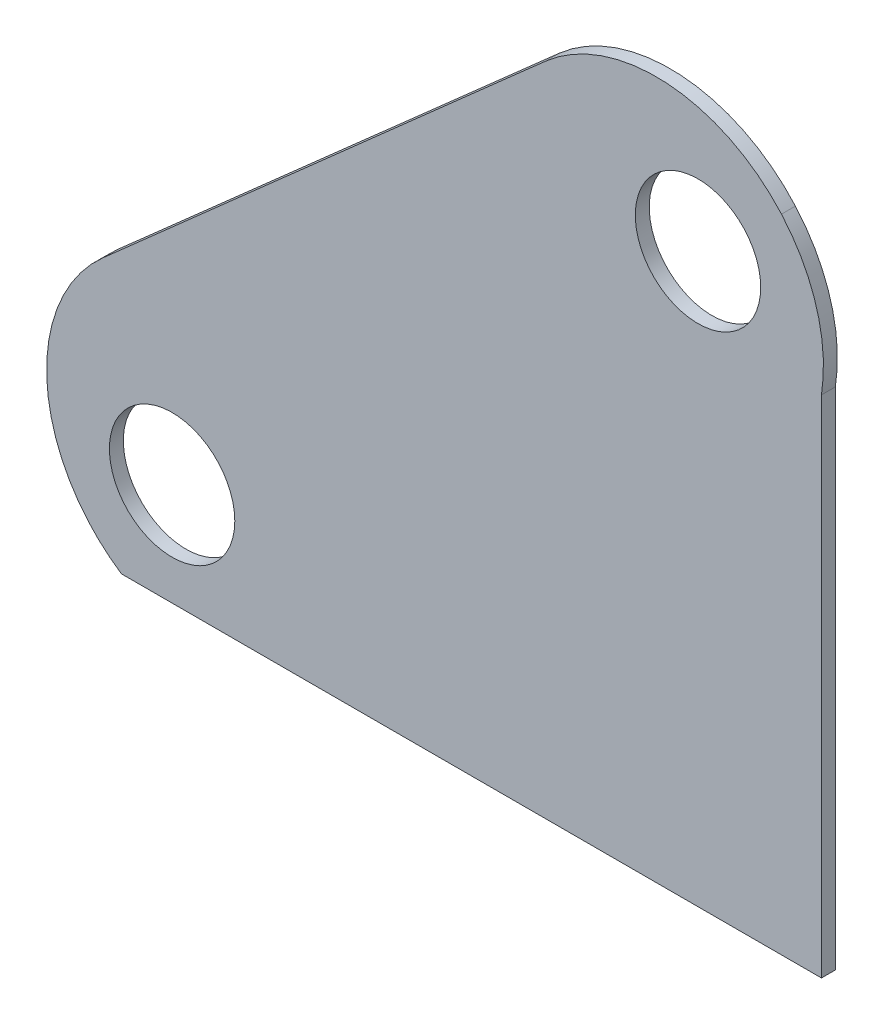
SolidWorks part; units mm, degrees
ref_plane "Front Plane" through (0, 0, 0) normal (0, 0, 1) x (1, 0, 0)
ref_plane "Top Plane" through (0, 0, 0) normal (0, 1, 0) x (1, 0, 0)
ref_plane "Right Plane" through (0, 0, 0) normal (1, 0, 0) x (0, 0, -1)
sketch "Sketch1" plane through (0, 0, 0) normal (0, 0, 1) x (1, 0, 0)
  line L0 (-87.2741, 72.7462) -> (-207.1137, -33.2765)
  line L1 (-87.2741, 72.7462) -> (-137.7651, 129.8172)
  line L2 (-207.1137, -33.2765) -> (-257.6047, 23.7945)
  line L3 (-137.7651, 129.8172) -> (-257.6047, 23.7945)
  line L4 (-137.7651, 129.8172) -> (-118.7415, 146.6475)
  line L5 (-137.7651, 129.8172) -> (-87.2741, 72.7462)
  line L6 (-118.7415, 146.6475) -> (-68.2504, 89.5765)
  line L7 (-87.2741, 72.7462) -> (-68.2504, 89.5765)
  line L8 (-276.6283, 6.9641) -> (-257.6047, 23.7945)
  line L9 (-276.6283, 6.9641) -> (-226.1373, -50.1069)
  line L10 (-257.6047, 23.7945) -> (-207.1137, -33.2765)
  line L11 (-226.1373, -50.1069) -> (-207.1137, -33.2765)
  line L12 (-93.4959, 118.112) -> (-251.3828, -21.5714) construction
  circle A0 centre (-232.3592, -4.741) radius 14.2875
  circle A1 centre (-112.5196, 101.2817) radius 14.2875
  dimension "D2" = 28.575
  dimension "D1" = 210.8073
  dimension "D3" = 76.2
  dimension "D4" = 25.4
  dimension "D5" = 25.4
extrude "Boss-Extrude1" add sketch "Sketch1" along normal blind 3.175 contours L12 A1 L1 L3 L2 A0 | A1 L12 A0 L2 L0 L1 | A0 L12 L9 L11 L2 | L12 A0 L2 L8 L9 | L12 L6 L4 L1 A1 | L6 L12 A1 L1 L7 region at (-159.3389, 33.4626, 0) region at (-87.6895, 94.371, 0) region at (-228.5265, -30.2284, 0) region at (-185.5399, 63.078, 0) region at (-116.3522, 126.769, 0) region at (-257.1893, 2.1697, 0)
fillet "Fillet1" radius 38.1 4 edges at (-276.6283, 6.9641, 1.5875) (-226.1373, -50.1069, 1.5875) (-68.2504, 89.5765, 1.5875) (-118.7415, 146.6475, 1.5875)
sketch "Sketch2" plane through (0, 0, 3.175) normal (0, 0, 1) x (1, 0, 0)
  line L0 (-96.7859, 64.331) -> (-197.6018, -24.8614) construction
  line L1 (-243.9079, -28.0759) -> (-201.2352, -28.0759)
  line L2 (-243.9079, -28.0759) -> (-243.9079, -34.4259)
  line L3 (-243.9079, -34.4259) -> (-201.2352, -34.4259)
  line L4 (-201.2352, -28.0759) -> (-201.2352, -34.4259)
  arc A0 (-251.3828, -21.5714) -> (-197.6018, -24.8614) centre (-222.8473, 3.6741) ccw construction
  point P7 (0, 0)
  point P10 (0, 0)
  point P11 (-248.1621, -24.8)
  point P12 (0, 0)
  dimension "D1" = 6.35
extrude "Cut-Extrude1" cut sketch "Sketch2" against normal blind 3.175 body kept at (-93.4959, 118.1119, 0)
sketch "Sketch3" plane through (0, 0, 3.175) normal (0, 0, 1) x (1, 0, 0)
  line L0 (-177.4198, 94.7345) -> (-207.6817, 67.9616)
  line L1 (-201.7868, -28.0759) -> (-84.3867, -28.0759)
  line L2 (-201.7868, -28.0759) -> (-201.7868, 86.9942)
  line L3 (-201.7868, 86.9942) -> (-84.3867, 86.9942)
  line L4 (-84.3867, -28.0759) -> (-84.3867, 86.9942)
  line L5 (-147.2769, 121.402) -> (-248.0928, 32.2096) construction
  arc A0 (-96.7859, 64.331) -> (-93.4959, 118.112) centre (-122.0314, 92.8665) ccw construction
  arc M2 (-201.7868, -28.0759) -> (-197.6018, -24.8614) centre (-222.8473, 3.6741) ccw
  line M3 (-197.6018, -24.8614) -> (-96.7859, 64.331)
  arc M4 (-96.7859, 64.331) -> (-93.4959, 118.112) centre (-122.0314, 92.8665) ccw
extrude "Boss-Extrude2" add sketch "Sketch3" against normal blind 3.175 contours L1 L4 M4 M3 M2 region at (-123.1437, 6.7622, 3.175)
